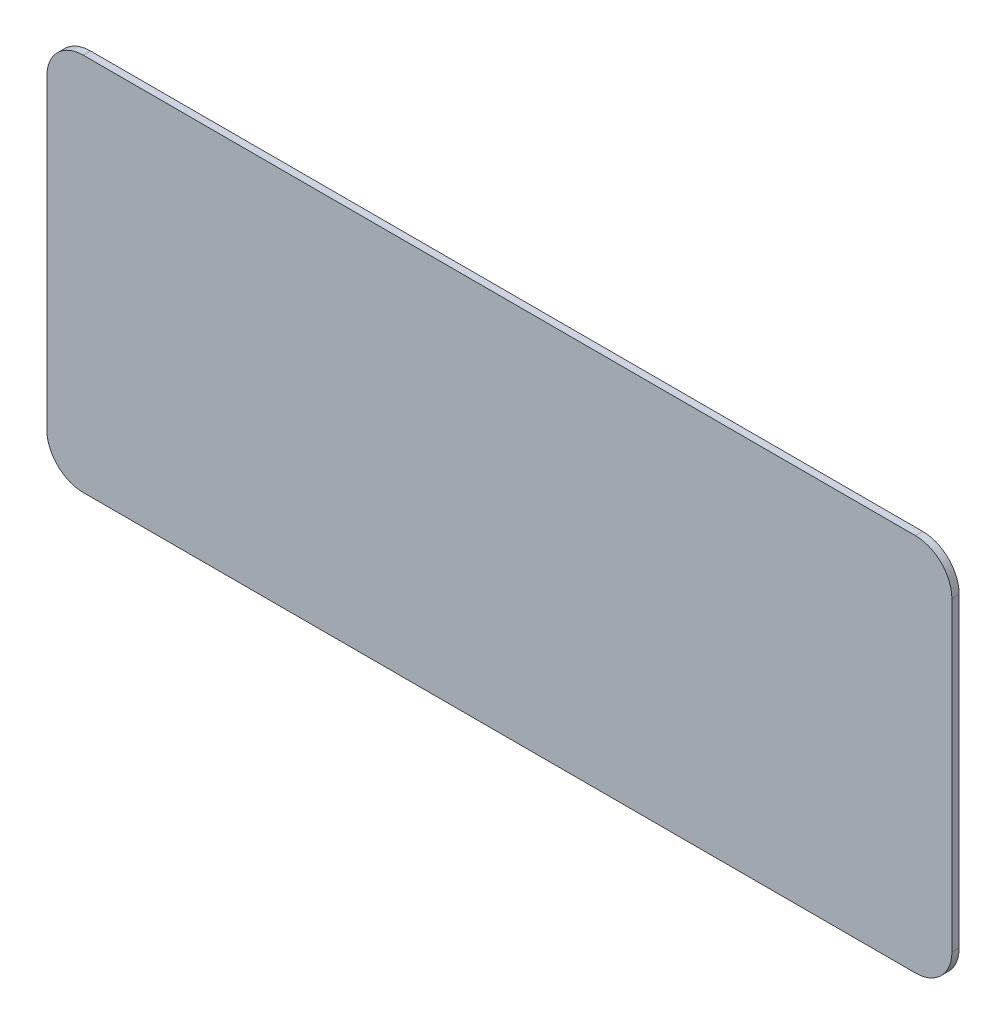
SolidWorks part; units mm, degrees
material "Acrylic (Medium-high impact)"
ref_plane "Front Plane" through (0, 0, 0) normal (0, 0, 1) x (1, 0, 0)
ref_plane "Top Plane" through (0, 0, 0) normal (0, 1, 0) x (1, 0, 0)
ref_plane "Right Plane" through (0, 0, 0) normal (1, 0, 0) x (0, 0, -1)
sketch "Sketch1" plane through (0, 0, 0) normal (0, 0, 1) x (1, 0, 0)
  line L1 (-243.5, -99) -> (243.5, -99) construction
  line L2 (-243.5, -99) -> (-243.5, 99) construction
  line L3 (-243.5, 99) -> (243.5, 99) construction
  line L4 (243.5, -99) -> (243.5, 99) construction
  line L5 (-243.5, -99) -> (243.5, 99) construction
  line L6 (-243.5, 99) -> (243.5, -99) construction
  line L7 (-248.5, -104) -> (248.5, -104)
  line L8 (-248.5, -104) -> (-248.5, 104)
  line L9 (-248.5, 104) -> (248.5, 104)
  line L10 (248.5, -104) -> (248.5, 104)
  line L11 (-248.5, -104) -> (248.5, 104) construction
  line L12 (-248.5, 104) -> (248.5, -104) construction
  point P0 (0, 0)
  dimension "D1" = 487
  dimension "D2" = 198
  dimension "D3" = 5
  dimension "D4" = 5
extrude "Boss-Extrude1" add sketch "Sketch1" along normal blind 4
fillet "Fillet1" radius 20 4 edges at (-248.5, -104, 2) (-248.5, 104, 2) (248.5, 104, 2) (248.5, -104, 2)
